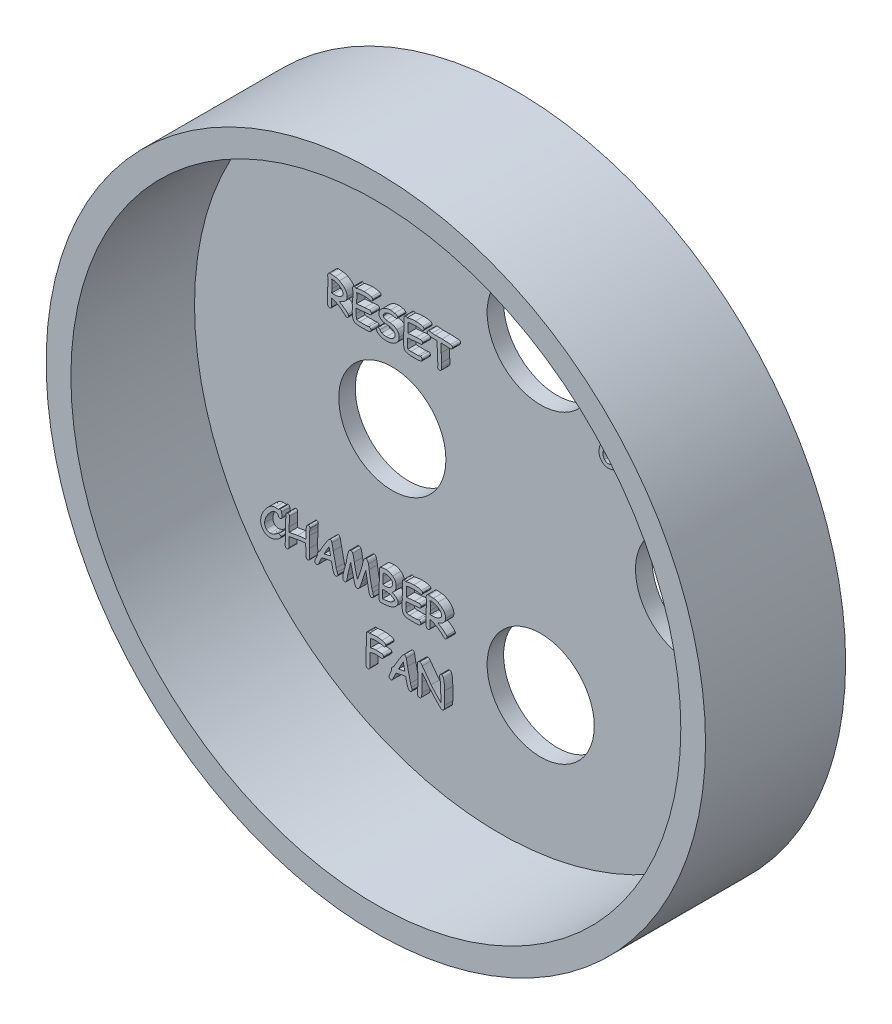
SolidWorks part; units mm, degrees
ref_plane "Front Plane" through (0, 0, 0) normal (0, 0, 1) x (1, 0, 0)
ref_plane "Top Plane" through (0, 0, 0) normal (0, 1, 0) x (1, 0, 0)
ref_plane "Right Plane" through (0, 0, 0) normal (1, 0, 0) x (0, 0, -1)
sketch "Esquisse1" plane through (0, 0, 0) normal (0, 0, 1) x (1, 0, 0)
  circle A0 centre (0, 0) radius 37
  circle A1 centre (0, 0) radius 40
extrude "Boss.-Extru.1" add sketch "Esquisse1" along normal blind 15
sketch "Esquisse3" plane through (0, 0, 0) normal (0, 0, 1) x (1, 0, 0)
  circle A0 centre (0, 0) radius 40
extrude "Boss.-Extru.2" add sketch "Esquisse3" against normal blind 2
sketch "Esquisse4" plane through (0, 0, 0) normal (0, 0, 1) x (1, 0, 0)
  circle A2 centre (0, 0) radius 6.5
  point P11 (0, 0)
  point P12 (0, 0)
  point P13 (-8.1238, -10.2017)
  point P14 (0, 0)
  point P15 (0, 0)
sketch "Esquisse5" plane through (0, 0, 0) normal (0, 0, 1) x (1, 0, 0)
  circle A0 centre (-13, -1) radius 6.5
  point P2 (-13.08, -4.8796)
extrude "Enlèv. mat.-Extru.4" cut sketch "Esquisse5" against normal blind 2
sketch "Esquisse7" plane through (0, 0, 0) normal (0, 0, 1) x (1, 0, 0)
  circle A0 centre (23, -1) radius 6.5
  point P2 (0, 0)
extrude "Enlèv. mat.-Extru.5" cut sketch "Esquisse7" against normal blind 2
sketch "Esquisse8" plane through (0, 0, 0) normal (0, 0, 1) x (1, 0, 0)
  circle A0 centre (5, -20) radius 6.5
  point P2 (0, 0)
  point P3 (0, 0)
  point P4 (9.5921, -18.957)
  point P6 (0, 0)
extrude "Enlèv. mat.-Extru.6" cut sketch "Esquisse8" against normal blind 2
sketch "Esquisse9" plane through (0, 0, 0) normal (0, 0, 1) x (1, 0, 0)
  circle A0 centre (5, 17) radius 6.5
  point P2 (6.5, 16.8005)
  point P4 (9.7402, 18.0889)
  point P6 (0, 0)
  dimension "D1" = 5
extrude "Enlèv. mat.-Extru.7" cut sketch "Esquisse9" against normal blind 2
sketch "Esquisse12" plane through (0, 0, 0) normal (0, 0, 1) x (1, 0, 0)
  text T0 "RESET" font "Comic Sans MS" height 3.5
  dimension "D1" = 9
extrude "Boss.-Extru.3" add sketch "Esquisse12" along normal blind 1
sketch "Esquisse13" plane through (0, 0, 0) normal (0, 0, 1) x (1, 0, 0)
  text T0 "CPU FAN" font "Comic Sans MS" height 3.5
  point P1 (0, 0)
  point P3 (14.1858, 9)
  point P4 (0, 0)
  point P5 (0, 0)
  dimension "D1" = 9
extrude "Boss.-Extru.4" add sketch "Esquisse13" along normal blind 1
sketch "Esquisse16" plane through (0, 0, 0) normal (0, 0, 1) x (1, 0, 0)
  text T0 "LIGHT" font "Comic Sans MS" height 3.5
  dimension "D1" = 27
extrude "Boss.-Extru.5" add sketch "Esquisse16" along normal blind 1
sketch "Esquisse17" plane through (0, 0, 0) normal (0, 0, 1) x (1, 0, 0)
  text T0 "CHAMBER\r\n         FAN" font "Comic Sans MS" height 3.5
extrude "Boss.-Extru.6" add sketch "Esquisse17" along normal blind 1
